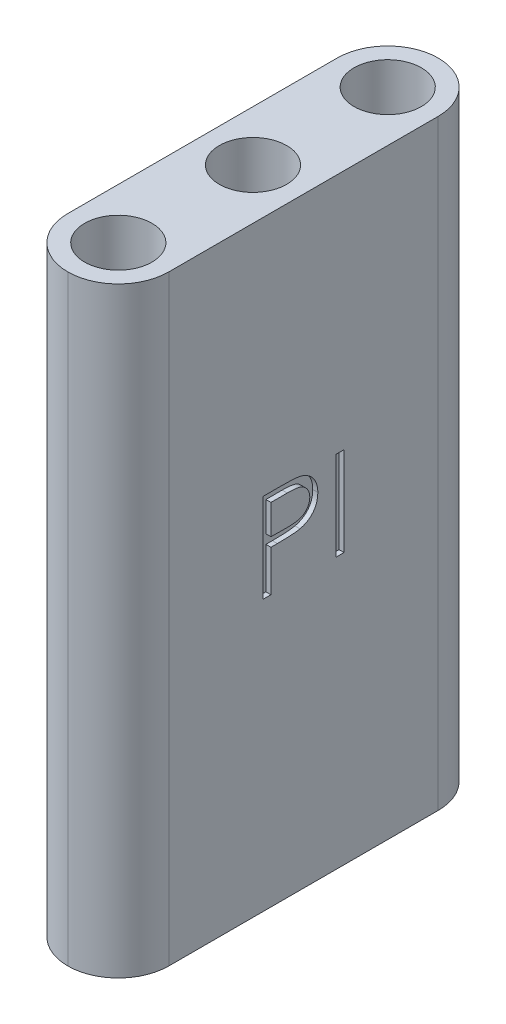
SolidWorks part; units mm, degrees
ref_plane "Front Plane" through (0, 0, 0) normal (0, 0, 1) x (1, 0, 0)
ref_plane "Top Plane" through (0, 0, 0) normal (0, 1, 0) x (1, 0, 0)
ref_plane "Right Plane" through (0, 0, 0) normal (1, 0, 0) x (0, 0, -1)
sketch "Sketch1" plane through (0, 0, 0) normal (0, 1, 0) x (1, 0, 0)
  line L0 (3, -22) -> (3, 0) construction
  line L1 (0, 0) -> (6, 0)
  line L2 (0, 0) -> (0, -22)
  line L3 (0, -22) -> (6, -22)
  line L4 (6, 0) -> (6, -22)
  line L5 (0, -11) -> (6, -11) construction
  circle A0 centre (3, -11) radius 2
  circle A1 centre (3, -19) radius 2
  circle A2 centre (3, -3) radius 2
  dimension "D1" = 4
  dimension "D4" = 4
  dimension "D5" = 3
  dimension "D3" = 3
  dimension "D2" = 8
extrude "Boss-Extrude1" add sketch "Sketch1" along normal blind 35.7
fillet "Fillet1" radius 3 4 edges at (0, 17.85, 0) (6, 17.85, 0) (0, 17.85, 22) (6, 17.85, 22)
sketch "Sketch2" plane through (6, 0, 0) normal (1, 0, 0) x (0, 0, -1)
  text T0 "\r\n\r\nPI" font "Century Gothic" height in points 20
extrude "Cut-Extrude1" cut sketch "Sketch2" against normal blind 0.3
